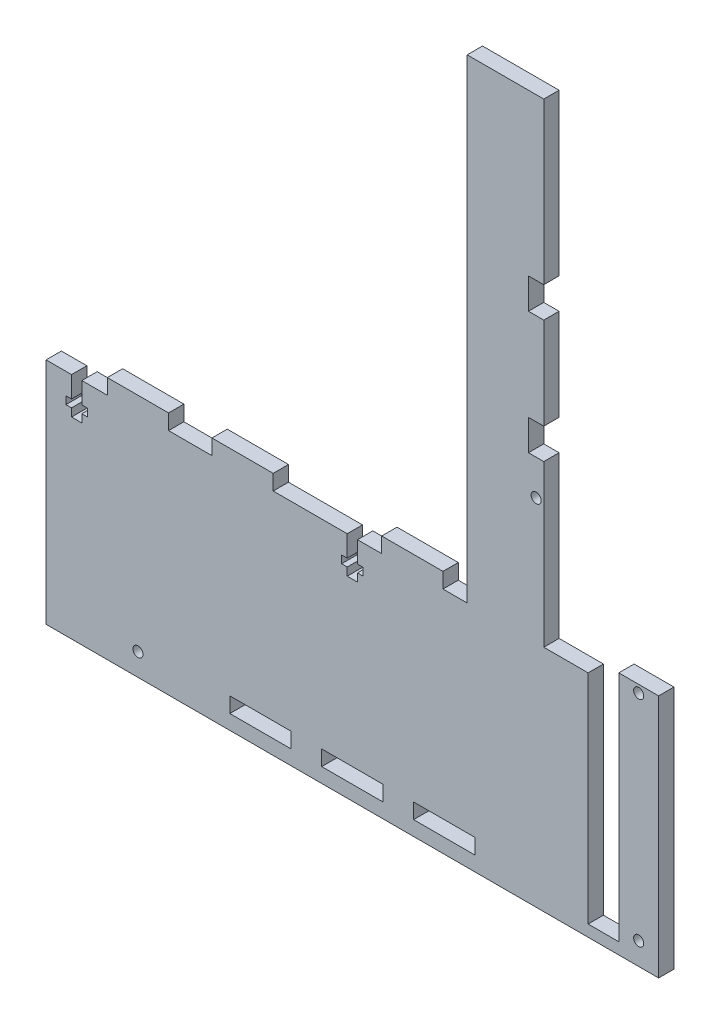
SolidWorks part; units mm, degrees
ref_plane "Front Plane" through (0, 0, 0) normal (0, 0, 1) x (1, 0, 0)
ref_plane "Top Plane" through (0, 0, 0) normal (0, 1, 0) x (1, 0, 0)
ref_plane "Right Plane" through (0, 0, 0) normal (1, 0, 0) x (0, 0, -1)
sketch "Sketch1" plane through (0, 0, 0) normal (0, 1, 0) x (1, 0, 0)
  line L0 (0, 15.4483) -> (0, 24.666) construction
  line L1 (-143.9938, 3.175) -> (110.0062, 3.175)
  line L2 (-143.9938, 3.175) -> (-143.9938, -3.175)
  line L3 (-143.9938, -3.175) -> (110.0062, -3.175)
  line L4 (110.0062, 3.175) -> (110.0062, -3.175)
  line L5 (8.1935, 0) -> (24.922, 0) construction
  dimension "D2" = 6.35
extrude "Base Extrusion" add sketch "Sketch1" along normal up to surface (94.9689 mm away)
sketch "Sketch4" plane through (0, 0, 3.175) normal (0, 0, 1) x (1, 0, 0)
  line L0 (110.0062, 12.4189) -> (-143.9938, 12.4189) construction
  line L1 (-67.7938, 12.4189) -> (-42.3938, 12.4189)
  line L2 (-67.7938, 12.4189) -> (-67.7938, 6.0689)
  line L3 (-67.7938, 6.0689) -> (-42.3938, 6.0689)
  line L4 (-42.3938, 12.4189) -> (-42.3938, 6.0689)
  line L5 (-29.6938, 12.4189) -> (-4.2938, 12.4189)
  line L6 (-29.6938, 12.4189) -> (-29.6938, 6.0689)
  line L7 (-29.6938, 6.0689) -> (-4.2938, 6.0689)
  line L8 (-4.2938, 12.4189) -> (-4.2938, 6.0689)
  line L9 (8.4062, 12.4189) -> (33.8062, 12.4189)
  line L10 (8.4062, 12.4189) -> (8.4062, 6.0689)
  line L11 (8.4062, 6.0689) -> (33.8062, 6.0689)
  line L12 (33.8062, 12.4189) -> (33.8062, 6.0689)
  line L13 (364.0062, 6.0689) -> (110.0062, 6.0689) construction
  line L14 (110.0062, 12.4189) -> (-143.9938, 12.4189) construction
  line L15 (364.0062, 6.0689) -> (110.0062, 6.0689) construction
  line L17 (-16.9938, 40.6411) -> (-16.9938, -10.2729) construction
  line L18 (-143.9938, 94.9689) -> (-143.9938, 0) construction
  line L19 (110.0062, 94.9689) -> (110.0062, 0) construction
  dimension "D1" = 25.4
  dimension "D2" = 25.4
  dimension "D3" = 25.4
  dimension "D5" = 12.7
  dimension "D6" = 12.7
extrude "Tab Holes to Chassis Base" cut sketch "Sketch4" against normal through all
sketch "Sketch5" plane through (0, 0, 3.175) normal (0, 0, 1) x (1, 0, 0)
  line L0 (-16.9938, 67.1576) -> (-16.9938, 113.4981) construction
  line L1 (-143.9938, 94.9689) -> (-143.9938, 0) construction
  line L2 (110.0062, 94.9689) -> (110.0062, 0) construction
  line L3 (110.0062, 94.9689) -> (-143.9938, 94.9689) construction
  line B0 (-14.8602, 94.9689) -> (-19.1274, 94.9689)
  line B1 (-19.1274, 83.0309) -> (-21.4388, 83.0309)
  line B2 (-21.4388, 83.0309) -> (-21.4388, 86.2059)
  line B3 (-21.4388, 86.2059) -> (-19.1274, 86.2059)
  line B4 (-19.1274, 86.2059) -> (-19.1274, 94.9689)
  line B5 (-19.1274, 83.0309) -> (-19.1274, 79.7289)
  line B6 (-19.1274, 79.7289) -> (-14.8602, 79.7289)
  line B7 (-14.8602, 83.0309) -> (-14.8602, 79.7289)
  line B8 (-14.8602, 86.2059) -> (-14.8602, 94.9689)
  line B9 (-12.5488, 86.2059) -> (-14.8602, 86.2059)
  line B10 (-12.5488, 83.0309) -> (-12.5488, 86.2059)
  line B11 (-14.8602, 83.0309) -> (-12.5488, 83.0309)
sketch_block_instance "TSlot-1"
sketch_block "TSlot" parameters "D1"=3.302, "D2"=3.175
extrude "T Slot Center" cut sketch "Sketch5" against normal through all
sketch "Sketch6" plane through (0, 0, 3.175) normal (0, 0, 1) x (1, 0, 0)
  line L0 (110.0062, 94.9689) -> (-14.8602, 94.9689) construction
  line L1 (62.3812, 94.9689) -> (30.6312, 94.9689)
  line L2 (62.3812, 94.9689) -> (62.3812, 291.8189)
  line L3 (62.3812, 291.8189) -> (30.6312, 291.8189)
  line L4 (30.6312, 94.9689) -> (30.6312, 291.8189)
  line L5 (62.3812, 12.4189) -> (62.3812, 144.9053) construction
  line L6 (56.0312, 291.8189) -> (62.3812, 291.8189) construction
  dimension "D1" = 31.75
extrude "Arm Support" add sketch "Sketch6" against normal up to surface (6.35 mm away) up to face at (-16.9938, 76.0175, -3.175)
sketch "Sketch8" plane through (0, 94.9689, 0) normal (0, 1, 0) x (1, 0, 0)
  line L0 (80.775, -3.175) -> (80.775, 3.175)
  line L1 (80.775, -3.175) -> (93.475, -3.175)
  line L2 (80.775, 3.175) -> (93.475, 3.175)
  line L3 (93.475, -3.175) -> (93.475, 3.175)
  line L4 (110.0062, -3.175) -> (62.3812, -3.175) construction
  line L5 (62.3812, 3.175) -> (110.0062, 3.175) construction
  line L6 (87.125, -7.9885) -> (87.125, 24.6597) construction
extrude "Arm Clearance" cut sketch "Sketch8" against normal offset from surface (90.2064 mm away) 4.7625 up to face at (-16.9938, 0, 0)
sketch "Sketch9" plane through (0, 0, 3.175) normal (0, 0, 1) x (1, 0, 0)
  line L0 (96.3524, 9.2439) -> (106.7258, 9.2439) construction
  line L3 (101.7406, 25.5557) -> (101.7406, 3.267) construction
  line L4 (93.475, 4.7625) -> (93.475, 94.9689) construction
  line L5 (110.0062, 94.9689) -> (110.0062, 0) construction
  circle A0 centre (101.7406, 9.2439) radius 2.0955
  dimension "D1" = 4.191
extrude "Base Mounting Hole 1" cut sketch "Sketch9" against normal through all
sketch "Sketch10" plane through (0, 0, 3.175) normal (0, 0, 1) x (1, 0, 0)
  line L0 (-78.6997, 9.2439) -> (-124.1873, 9.2439) construction
  line L5 (-42.3938, 12.4189) -> (-67.7938, 12.4189) construction
  line L6 (-67.7938, 6.0689) -> (-42.3938, 6.0689) construction
  line L7 (-105.8938, 38.7875) -> (-105.8938, -6.1881) construction
  line L8 (-143.9938, 94.9689) -> (-143.9938, 0) construction
  line L9 (-67.7938, 12.4189) -> (-67.7938, 6.0689) construction
  circle A0 centre (-105.8938, 9.2439) radius 2.0955
  circle A1 centre (101.7406, 9.2439) radius 2.0955 construction
extrude "Base Mounting Hole 2" cut sketch "Sketch10" against normal through all
sketch "Sketch11" plane through (0, 0, 3.175) normal (0, 0, 1) x (1, 0, 0)
  line L0 (39.2564, 147.0389) -> (78.7704, 147.0389) construction
  line L1 (62.3812, 149.1725) -> (56.0312, 149.1725) construction
  line L2 (56.0312, 144.9053) -> (62.3812, 144.9053) construction
  line L3 (59.2062, 189.1979) -> (59.2062, 134.4872) construction
  line L4 (62.3812, 291.8189) -> (62.3812, 94.9689) construction
  line L5 (56.0312, 149.1725) -> (56.0312, 161.6439) construction
  circle A0 centre (59.2062, 147.0389) radius 2.0955
  circle A1 centre (101.7406, 9.2439) radius 2.0955 construction
extrude "Arm Support Mounting Hole" cut sketch "Sketch11" against normal through all
sketch "Sketch12" plane through (0, 0, 3.175) normal (0, 0, 1) x (1, 0, 0)
  line L0 (62.3812, 94.9689) -> (62.3812, 291.8189) construction
  line L1 (56.0312, 225.1439) -> (62.3812, 225.1439)
  line L2 (56.0312, 225.1439) -> (56.0312, 212.4439)
  line L3 (56.0312, 212.4439) -> (62.3812, 212.4439)
  line L4 (62.3812, 225.1439) -> (62.3812, 212.4439)
  line L5 (56.0312, 174.3439) -> (62.3812, 174.3439)
  line L6 (56.0312, 174.3439) -> (56.0312, 161.6439)
  line L7 (56.0312, 161.6439) -> (62.3812, 161.6439)
  line L8 (62.3812, 174.3439) -> (62.3812, 161.6439)
  line L9 (56.0312, 161.6439) -> (56.0312, 174.3439) construction
  line L10 (56.0312, 174.3439) -> (62.3812, 174.3439) construction
  line L11 (62.3812, 161.6439) -> (56.0312, 161.6439) construction
  line L12 (56.0312, 212.4439) -> (56.0312, 225.1439) construction
  line L13 (56.0312, 225.1439) -> (62.3812, 225.1439) construction
  line L14 (62.3812, 212.4439) -> (56.0312, 212.4439) construction
extrude "Arm Support Tab Slots" cut sketch "Sketch12" against normal through all
sketch "Sketch13" plane through (0, 94.9689, 0) normal (0, 1, 0) x (1, 0, 0)
  line L0 (-143.9938, 3.175) -> (-19.1274, 3.175) construction
  line L1 (93.475, 3.175) -> (110.0062, 3.175)
  line L2 (93.475, 3.175) -> (93.475, -3.175)
  line L3 (93.475, -3.175) -> (110.0062, -3.175)
  line L4 (110.0062, 3.175) -> (110.0062, -3.175)
  line L5 (-118.5938, 3.175) -> (-93.1938, 3.175)
  line L6 (-118.5938, 3.175) -> (-118.5938, -3.175)
  line L7 (-118.5938, -3.175) -> (-93.1938, -3.175)
  line L8 (-93.1938, 3.175) -> (-93.1938, -3.175)
  line L9 (-19.1274, -3.175) -> (-143.9938, -3.175) construction
  line L10 (-14.8602, 3.175) -> (30.6312, 3.175) construction
  line L11 (-4.8145, 3.175) -> (20.5855, 3.175)
  line L12 (-4.8145, 3.175) -> (-4.8145, -3.175)
  line L13 (-4.8145, -3.175) -> (20.5855, -3.175)
  line L14 (20.5855, 3.175) -> (20.5855, -3.175)
  line L15 (30.6312, -3.175) -> (-14.8602, -3.175) construction
  line L16 (7.8855, 19.4293) -> (7.8855, -15.2554) construction
  line L17 (-75.2106, 3.175) -> (-49.8106, 3.175)
  line L18 (-75.2106, 3.175) -> (-75.2106, -3.175)
  line L19 (-75.2106, -3.175) -> (-49.8106, -3.175)
  line L20 (-49.8106, 3.175) -> (-49.8106, -3.175)
  line L21 (-14.8602, 3.175) -> (-14.8602, -3.175) construction
  line L22 (30.6312, 3.175) -> (30.6312, -3.175) construction
  line L23 (-105.8938, 22.3632) -> (-105.8938, -15.2554) construction
  line L28 (-62.5106, 22.3632) -> (-62.5106, -21.1411) construction
  line L29 (-19.1274, 3.175) -> (-19.1274, -3.175) construction
  dimension "D1" = 25.4
extrude "Top Plate Tab" add sketch "Sketch13" along normal blind 6.35
sketch "Sketch14" plane through (0, 0, 3.175) normal (0, 0, 1) x (1, 0, 0)
  line L0 (-131.2938, 71.8951) -> (-131.2938, 106.4008) construction
  line L1 (-118.5938, 94.9689) -> (-143.9938, 94.9689) construction
  line L2 (-143.9938, 94.9689) -> (-143.9938, 0) construction
  line L3 (-118.5938, 101.3189) -> (-118.5938, 94.9689) construction
  line B0 (-129.1602, 94.9689) -> (-133.4274, 94.9689)
  line B1 (-133.4274, 83.0309) -> (-135.7388, 83.0309)
  line B2 (-135.7388, 83.0309) -> (-135.7388, 86.2059)
  line B3 (-135.7388, 86.2059) -> (-133.4274, 86.2059)
  line B4 (-133.4274, 86.2059) -> (-133.4274, 94.9689)
  line B5 (-133.4274, 83.0309) -> (-133.4274, 79.7289)
  line B6 (-133.4274, 79.7289) -> (-129.1602, 79.7289)
  line B7 (-129.1602, 83.0309) -> (-129.1602, 79.7289)
  line B8 (-129.1602, 86.2059) -> (-129.1602, 94.9689)
  line B9 (-126.8488, 86.2059) -> (-129.1602, 86.2059)
  line B10 (-126.8488, 83.0309) -> (-126.8488, 86.2059)
  line B11 (-129.1602, 83.0309) -> (-126.8488, 83.0309)
sketch_block_instance "TSlot-3"
extrude "T Slot Top Corner" cut sketch "Sketch14" against normal through all
sketch "Sketch15" plane through (0, 0, 3.175) normal (0, 0, 1) x (1, 0, 0)
  line L0 (101.7406, 99.797) -> (101.7406, 89.693) construction
  line L1 (93.475, 4.7625) -> (93.475, 101.3189) construction
  line L2 (110.0062, 101.3189) -> (110.0062, 0) construction
  line L3 (95.644, 98.1439) -> (106.8624, 98.1439) construction
  line L7 (62.3812, 94.9689) -> (80.775, 94.9689) construction
  line L8 (-4.8145, 101.3189) -> (20.5855, 101.3189) construction
  circle A0 centre (101.7406, 98.1439) radius 2.0955
  dimension "D1" = 4.191
extrude "Cut-Extrude8" cut sketch "Sketch15" against normal through all
